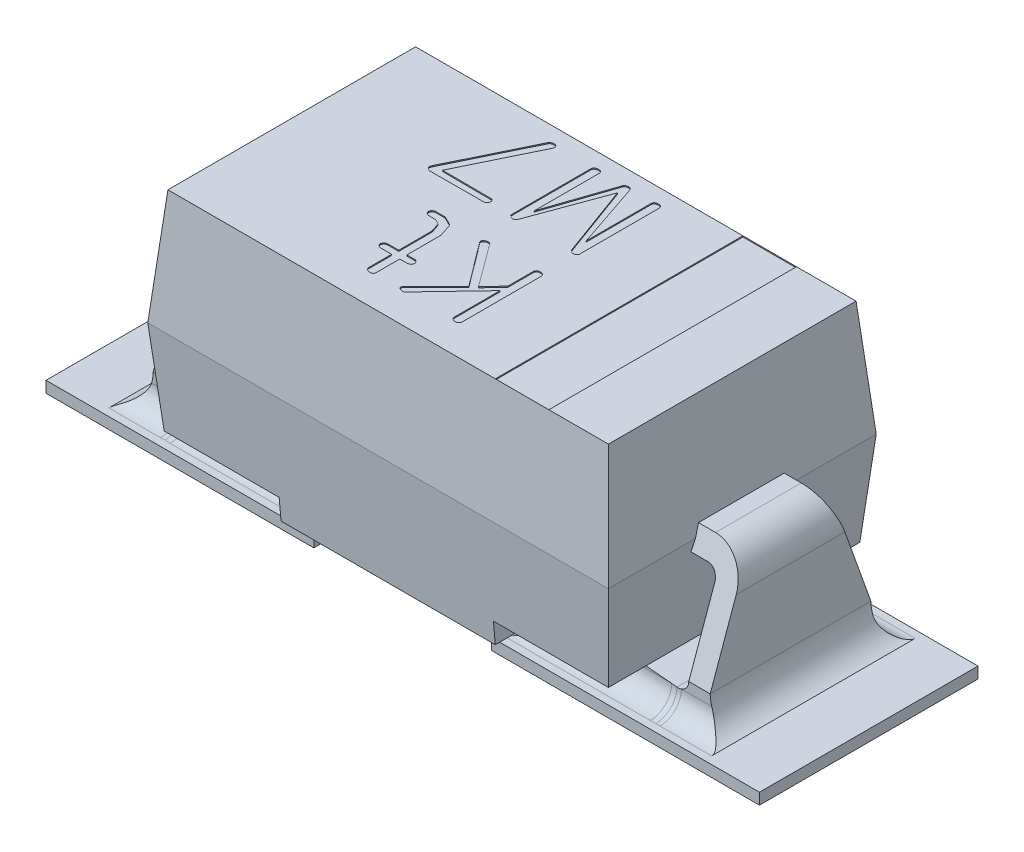
SolidWorks part; units mm, degrees
material "6063-O"
ref_plane "Front Plane" through (0, 0, 0) normal (0, 0, 1) x (1, 0, 0)
ref_plane "Top Plane" through (0, 0, 0) normal (0, 1, 0) x (1, 0, 0)
ref_plane "Right Plane" through (0, 0, 0) normal (1, 0, 0) x (0, 0, -1)
sketch "Sketch5" plane through (0, 0, 0) normal (0, 0, 1) x (1, 0, 0)
  line L2 (-2.3, 1.28) -> (2.3, 1.28)
  line L3 (2.5, 1.08) -> (2.5, 0.4)
  line L4 (2.2817, 0.2008) -> (1.2, 0.3)
  line L5 (0, -1.193) -> (0, 1.193) construction
  line L6 (1.375, 0) -> (-1.375, 0) construction
  line L7 (2.3, 0.4) -> (2.3, 0.2) construction
  line L10 (-2.5, 1.08) -> (-2.5, 0.4)
  line L11 (-2.2817, 0.2008) -> (-1.2, 0.3)
  arc A0 (2.3, 1.28) -> (2.5, 1.08) centre (2.3, 1.08) cw
  arc A1 (2.5, 0.4) -> (2.2817, 0.2008) centre (2.3, 0.4) cw
  arc A2 (-2.5, 0.4) -> (-2.2817, 0.2008) centre (-2.3, 0.4) ccw
  arc A4 (-2.3, 1.28) -> (-2.5, 1.08) centre (-2.3, 1.08) ccw
  point P15 (2.5, 0.1808)
  dimension "D8" = 0.2
  dimension "D1" = 0.2
  dimension "D2" = 2.5
  dimension "D3" = 1.28
  dimension "D4" = 0.2
  dimension "D5" = 0.3
  dimension "D6" = 1.3
  dimension "D7" = 5
  dimension "D9" = 1.3
ref_plane "Plane4" through (1.2, 0.3, 0) normal (-0.9958, 0.0913, 0) x (0, 0, 1)
sketch "Sketch10" plane through (1.2, 0.3, 0) normal (-0.9958, 0.0913, 0) x (0, 0, 1)
  line L0 (-0.75, 0) -> (0.75, 0) construction
  line L2 (-0.75, 0.1) -> (0.75, 0.1)
  line L3 (-0.75, 0.1) -> (-0.75, -0.1)
  line L4 (-0.75, -0.1) -> (0.75, -0.1)
  line L5 (0.75, 0.1) -> (0.75, -0.1)
  dimension "D1" = 0.2
  dimension "D2" = 1.5
sketch "Sketch2" plane through (0, 0, 0) normal (0, 0, 1) x (1, 0, 0)
  line L0 (-2.15, 1.275) -> (-2.0559, 2.35)
  line L2 (-2.15, 1.275) -> (-2.0734, 0.4)
  line L4 (-2.0559, 2.35) -> (2.0559, 2.35)
  line L5 (-2.15, 1.275) -> (2.15, 1.275) construction
  line L7 (2.15, 1.275) -> (2.0559, 2.35)
  line L8 (-1, 0.2) -> (1, 0.2)
  line L9 (2.75, 0) -> (-2.75, 0) construction
  line L11 (2.0734, 0.4) -> (2.15, 1.275)
  line L12 (2.0734, 0.4) -> (1, 0.4)
  line L13 (1, 0.4) -> (1, 0.2)
  line L16 (-2.0734, 0.4) -> (-1, 0.4)
  line L17 (-1, 0.4) -> (-1, 0.2)
  line L19 (0, -0.6045) -> (0, 0.6045) construction
  dimension "D1" = 1.275
  dimension "D2" = 5
  dimension "D3" = 5
  dimension "D4" = 2.35
  dimension "D5" = 0.2
  dimension "D6" = 2
  dimension "D7" = 1
  dimension "D8" = 4.3
  dimension "D9" = 2.15
  dimension "D10" = 0.2
sweep "Sweep3" add profiles "Sketch10" path "Sketch5"
sketch "Sketch14" plane through (0, 0, 0) normal (1, 0, 0) x (0, 0, -1)
  line L0 (-0.75, 0.4) -> (-0.4, 1.38)
  line L1 (0.75, 1.38) -> (-0.75, 1.38) construction
  line L2 (-0.4, 1.38) -> (-0.75, 1.38)
  line L3 (-0.75, 1.38) -> (-0.75, 0.4)
  line L5 (0.4, 1.38) -> (0.75, 1.38)
  line L6 (0.75, 1.38) -> (0.75, 0.4)
  line L7 (0.75, 0.4) -> (0.4, 1.38)
  line L8 (0, 1.275) -> (0, 2.35) construction
  dimension "D1" = 0.8
  dimension "D2" = 0.4
extrude "Cut-Extrude4" cut sketch "Sketch14" against normal through all and the other way through all
extrude "Boss-Extrude2" add sketch "Sketch2" along normal mid plane 2.5
sketch "Sketch1" plane through (0, 0, 0) normal (1, 0, 0) x (0, 0, -1)
  line L0 (1.25, 0.4) -> (1.25, 1.275) construction
  line L1 (0, 0.6045) -> (0, -0.6045) construction
  line L3 (-1.25, 1.275) -> (-1.1559, 0.2)
  line L4 (2.75, 0) -> (-2.75, 0) construction
  line L5 (1.1559, 0.2) -> (1.25, 1.275)
  line L6 (1.25, 1.275) -> (1.1559, 2.35)
  line L7 (-1.25, 2.35) -> (1.25, 2.35) construction
  line L8 (-1.1559, 2.35) -> (-1.25, 1.275)
  line L9 (-1.25, 0.2) -> (1.25, 0.2) construction
  line L10 (1.1559, 2.35) -> (1.35, 2.35)
  line L11 (1.35, 2.35) -> (1.35, 0.2)
  line L12 (1.35, 0.2) -> (1.1559, 0.2)
  line L13 (-1.1559, 2.35) -> (-1.35, 2.35)
  line L14 (-1.35, 2.35) -> (-1.35, 0.2)
  line L15 (-1.35, 0.2) -> (-1.1559, 0.2)
  dimension "D1" = 2.5
  dimension "D2" = 1.25
  dimension "D3" = 1.275
  dimension "D4" = 0.1
  dimension "D5" = 0.1
  dimension "D6" = 5
  dimension "D7" = 5
extrude "Cut-Extrude5" cut sketch "Sketch1" against normal through all and the other way through all
sketch "Sketch15" plane through (0, 0, 0) normal (0, 1, 0) x (1, 0, 0)
  line L0 (0, -1.2375) -> (0, 1.2375) construction
  line L1 (-3.33, 1.02) -> (-0.83, 1.02)
  line L2 (-3.33, 1.02) -> (-3.33, -1.02)
  line L3 (-3.33, -1.02) -> (-0.83, -1.02)
  line L4 (-0.83, 1.02) -> (-0.83, -1.02)
  line L5 (0.83, 1.02) -> (3.33, 1.02)
  line L6 (0.83, 1.02) -> (0.83, -1.02)
  line L7 (0.83, -1.02) -> (3.33, -1.02)
  line L8 (3.33, 1.02) -> (3.33, -1.02)
  line L9 (-2.2817, 0) -> (-1.2, 0) construction
  dimension "D1" = 0.83
  dimension "D2" = 0.83
  dimension "D3" = 2.5
  dimension "D4" = 2.04
  dimension "D5" = 1.02
extrude "Boss-Extrude4" add sketch "Sketch15" along normal blind 0.105
sketch "Sketch16" plane through (0, 0, 0) normal (0, 0, 1) x (1, 0, 0)
  line L0 (0.83, 0) -> (2.83, 0)
  line L1 (1.375, 0) -> (-1.375, 0) construction
  line L2 (2.83, 0) -> (2.83, 0.1)
  line L3 (0.83, 0) -> (0.83, 0.1)
  line L4 (0, -1.2925) -> (0, 1.2925) construction
  line L5 (2.2817, 0.2008) -> (1.2, 0.3) construction
  line L6 (-0.83, 0.1) -> (-0.83, 0)
  line L8 (-2.83, 0) -> (-0.83, 0)
  line L9 (-2.83, 0) -> (-2.83, 0.1)
  line L11 (-1.1909, 0.2004) -> (-1.2091, 0.3996) construction
  arc A0 (2.83, 0.1) -> (2.6, 0.4) centre (2.9107, 0.4) cw
  arc A1 (2.6, 0.4) -> (1.2, 0.3) centre (1.8015, 1.7285) cw
  arc A2 (1.2, 0.3) -> (0.83, 0.1) centre (0.83, 0.5423) cw
  arc A3 (-2.83, 0.1) -> (-2.6, 0.4) centre (-2.9107, 0.4) ccw
  arc A4 (-1.2, 0.3) -> (-0.83, 0.1) centre (-0.83, 0.5423) ccw
  arc A5 (-2.6, 0.4) -> (-1.2, 0.3) centre (-1.8015, 1.7285) ccw
  dimension "D4" = 0.3107
  dimension "D5" = 1.55
  dimension "D6" = 1.55
  dimension "D1" = 0.1
  dimension "D2" = 0.83
  dimension "D3" = 2
  dimension "D7" = 0.1
  dimension "D8" = 2
  dimension "D9" = 0.83
extrude "Boss-Extrude8" add sketch "Sketch16" along normal mid plane 1.5
fillet "Fillet2" radius 0.2 4 edges at (1.8548, 0.105, -0.75) (-1.8548, 0.105, -0.75) (1.8548, 0.105, 0.75) (-1.8548, 0.105, 0.75)
sketch "Sketch19" plane through (0, 2.35, 0) normal (0, 1, 0) x (1, 0, 0)
  line L0 (-2.0559, 1.1559) -> (2.0559, 1.1559) construction
  line L1 (1, 1.1559) -> (1.5, 1.1559)
  line L2 (1, 1.1559) -> (1, -1.1559)
  line L3 (1, -1.1559) -> (1.5, -1.1559)
  line L4 (1.5, 1.1559) -> (1.5, -1.1559)
  line L5 (-2.0559, -1.1559) -> (2.0559, -1.1559) construction
  line L6 (0, -1.2925) -> (0, 1.2925) construction
  dimension "D1" = 0.5
  dimension "D2" = 1.5
extrude "Cut-Extrude6" cut sketch "Sketch19" against normal blind 0.01
sketch "Sketch20" plane through (0, 2.35, 0) normal (0, 1, 0) x (1, 0, 0)
  line L0 (0.5, 1) -> (-1.3, 1) construction
  line L1 (0.5, -0.1) -> (-1.3, -0.1) construction
  line L2 (0, -1.2925) -> (0, 1.2925) construction
  line L3 (-1.2925, 0) -> (1.2925, 0) construction
  text T0 "Kt" font "SWRomns" height 0.8
  text T1 "M7" font "SWRomns" height 0.8
  dimension "D1" = 0.5
  dimension "D2" = 0.5
  dimension "D3" = 0.1
  dimension "D4" = 1
  dimension "D5" = 1.8
extrude "Cut-Extrude7" cut sketch "Sketch20" against normal blind 0.01
